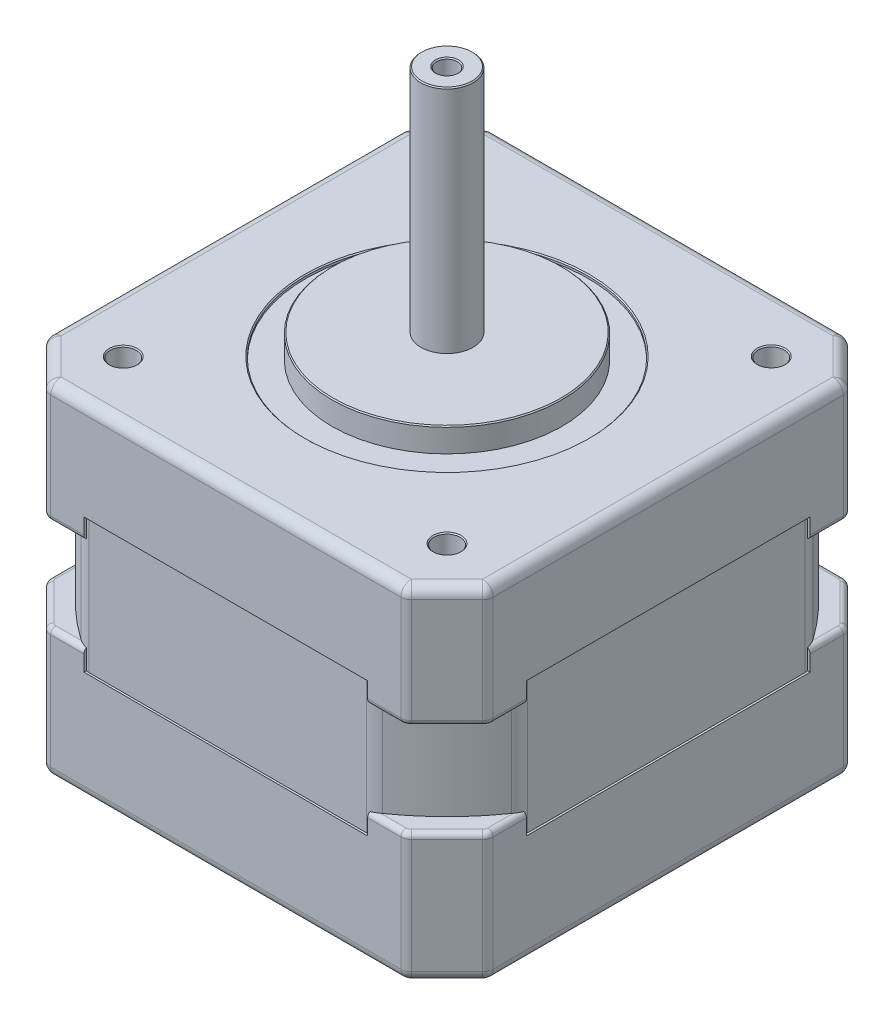
SolidWorks part; units mm, degrees
ref_plane "Front Plane" through (0, 0, 0) normal (0, 0, 1) x (1, 0, 0)
ref_plane "Top Plane" through (0, 0, 0) normal (0, 1, 0) x (1, 0, 0)
ref_plane "Right Plane" through (0, 0, 0) normal (1, 0, 0) x (0, 0, -1)
sketch "Sketch1" plane through (0, 0, 0) normal (0, 1, 0) x (1, 0, 0)
  line L0 (0, 21.15) -> (0, 0) construction
  line L1 (-21.15, 21.15) -> (-21.15, -21.15)
  line L2 (-21.15, -21.15) -> (21.15, -21.15)
  line L3 (-21.15, 21.15) -> (21.15, 21.15)
  line L4 (21.15, -21.15) -> (21.15, 21.15)
  line L5 (21.15, 0) -> (0, 0) construction
  line L6 (21.15, 21.15) -> (0, 0) construction
  circle A0 centre (15.5, 15.5) radius 1.25
  circle A1 centre (-15.4497, 15.5) radius 1.25
  circle A2 centre (-15.4497, -15.5) radius 1.25
  circle A3 centre (15.5, -15.5) radius 1.25
  dimension "D1" = 42.3
  dimension "D3" = 2.5
  dimension "D2" = 31
extrude "Boss-Extrude1" add sketch "Sketch1" against normal blind 32.8
chamfer "Chamfer1" distance 4 angle 45 4 edges at (21.15, -16.4, 21.15) (-21.15, -16.4, 21.15) (-21.15, -16.4, -21.15) (21.15, -16.4, -21.15)
sketch "Sketch2" plane through (0, 0, 0) normal (0, 1, 0) x (1, 0, 0)
  circle A0 centre (0, 0) radius 11
  dimension "D1" = 22
extrude "Boss-Extrude2" add sketch "Sketch2" along normal blind 2
sketch "Sketch6" plane through (0, -32.8, 0) normal (0, -1, 0) x (1, 0, 0)
  line L0 (-17.15, 21.15) -> (17.15, 21.15) construction
  line L1 (-21.15, -17.15) -> (-21.15, 17.15) construction
  line L2 (-17.15, 21.15) -> (-21.15, 17.15) construction
  line L3 (-17.15, 21.15) -> (-21.15, 17.15)
  line L4 (-21.15, 13.5626) -> (-21.15, 17.15)
  line L5 (-17.15, 21.15) -> (-13.5626, 21.15)
  arc A0 (-13.5626, 21.15) -> (-21.15, 13.5626) centre (0, 0) ccw
  dimension "D1" = 25.125
extrude "Cut-Extrude2" cut sketch "Sketch6" against normal offset from surface (8.85 mm away) 11.5 from offset 12.45 up to face at (0, 0, 0) offset against normal yes
pattern_circular "CirPattern1" count 4 over 360 about axis through (0, 10.7303, 0) along (0, -1, 0) of "Cut-Extrude2"
sketch "Sketch7" plane through (-21.15, 0, 0) normal (-1, 0, 0) x (0, 0, 1)
  line L0 (13.5626, -11.5) -> (13.5626, -20.35) construction
  line L1 (-13.5626, -9.5) -> (13.5626, -9.5)
  line L2 (-13.5626, -9.5) -> (-13.5626, -11.5)
  line L3 (-13.5626, -22.35) -> (13.5626, -22.35)
  line L4 (13.5626, -9.5) -> (13.5626, -11.5)
  line L5 (-13.5626, -11.5) -> (-13.5626, -20.35) construction
  line L6 (-17.15, -11.5) -> (-13.5626, -11.5) construction
  line L7 (-13.5626, -20.35) -> (-17.15, -20.35) construction
  line L8 (-21.15, -11.5) -> (-13.5626, -11.5) construction
  line L9 (-17.3563, -11.5) -> (-13.5626, -11.5)
  line L10 (-17.3563, -11.5) -> (-17.3563, -20.35)
  line L11 (-17.3563, -20.35) -> (-13.5626, -20.35)
  line L12 (19.15, -11.5) -> (19.15, -20.35)
  line L13 (21.15, -20.35) -> (17.15, -20.35) construction
  line L14 (13.5626, -11.5) -> (19.15, -11.5)
  line L15 (-13.5626, -20.35) -> (-13.5626, -22.35)
  line L16 (13.5626, -20.35) -> (13.5626, -22.35)
  line L17 (13.5626, -20.35) -> (19.15, -20.35)
  dimension "D1" = 2
  dimension "D2" = 2
extrude "Cut-Extrude3" cut sketch "Sketch7" against normal blind 0.2
pattern_circular "CirPattern2" count 4 over 360 about axis through (0, 2, 0) along (0, -1, 0) of "Cut-Extrude3"
sketch "Sketch3" plane through (0, 0, 0) normal (0, 1, 0) x (1, 0, 0)
  circle A0 centre (0, 0) radius 2.5
  dimension "D1" = 5
extrude "Boss-Extrude3" add sketch "Sketch3" along normal blind 24
sketch "Sketch8" plane through (0, -32.8, 0) normal (0, -1, 0) x (1, 0, 0)
  circle A0 centre (15.5, -15.5) radius 3.075
  circle A1 centre (15.5, 15.5) radius 3.075
  circle A2 centre (-15.4497, 15.5) radius 3.075
  circle A3 centre (-15.4497, -15.5) radius 3.075
  dimension "D1" = 6.15
extrude "Cut-Extrude4" cut sketch "Sketch8" against normal blind 2
sketch "Sketch9" plane through (0, -32.8, 0) normal (0, -1, 0) x (1, 0, 0)
  circle A0 centre (0, 0) radius 4.625
  dimension "D1" = 9.25
extrude "Cut-Extrude5" cut sketch "Sketch9" against normal blind 3
sketch "Sketch10" plane through (0, 0, -21.15) normal (0, 0, -1) x (-1, 0, 0)
  line L0 (-13.5626, -22.35) -> (13.5626, -22.35) construction
  line L1 (-4.1, -30.55) -> (4.1, -30.55)
  line L2 (-4.1, -30.55) -> (-4.1, -22.35)
  line L3 (-4.1, -22.35) -> (4.1, -22.35)
  line L4 (4.1, -30.55) -> (4.1, -22.35)
  line L5 (-4.1, -30.55) -> (4.1, -22.35) construction
  line L6 (-4.1, -22.35) -> (4.1, -30.55) construction
  line L7 (0, -11.5) -> (0, -20.35) construction
  point P0 (0, -26.45)
  dimension "D1" = 8.2
extrude "Cut-Extrude6" cut sketch "Sketch10" against normal blind 0.5
sketch "Sketch11" plane through (0, 0, 0) normal (0, 1, 0) x (1, 0, 0)
  circle A0 centre (0, 0) radius 11 construction
  circle A1 centre (0, 0) radius 11
  circle A2 centre (0, 0) radius 13.5
  dimension "D1" = 2.5
extrude "Cut-Extrude7" cut sketch "Sketch11" against normal blind 0.3
fillet "Fillet2" radius 2 8 edges at (-13.8695, -15.925, -20.95) (13.8695, -15.925, -20.95) (20.95, -15.925, -13.8695) (20.95, -15.925, 13.8695) (13.8695, -15.925, 20.95) (-13.8695, -15.925, 20.95) (-20.95, -15.925, 13.8695) (-20.95, -15.925, -13.8695)
fillet "Fillet1" radius 1 32 edges at (0, 0, 21.15) (0, -32.8, 21.15) (19.15, 0, -19.15) (19.15, -32.8, -19.15) (17.15, -5.75, -21.15) (17.15, -26.575, -21.15) (0, 0, -21.15) (0, -32.8, -21.15) (-17.15, -5.75, -21.15) (-17.15, -26.575, -21.15) (-19.15, 0, -19.15) (-19.15, -32.8, -19.15) (-21.15, -5.75, -17.15) (-21.15, -26.575, -17.15) (-21.15, 0, 0) (-21.15, -32.8, 0) (-21.15, -5.75, 17.15) (-21.15, -26.575, 17.15) (-19.15, 0, 19.15) (-17.15, -5.75, 21.15) (-17.15, -26.575, 21.15) (-19.15, -32.8, 19.15) (21.15, -5.75, -17.15) (21.15, -26.575, -17.15) (21.15, -32.8, 0) (21.15, 0, 0) (17.15, -5.75, 21.15) (17.15, -26.575, 21.15) (19.15, 0, 19.15) (21.15, -5.75, 17.15) (21.15, -26.575, 17.15) (19.15, -32.8, 19.15)
fillet "Fillet3" radius 0.5 40 edges at (21.15, -11.5, -15.1492) (21.0739, -11.5, -17.1185) (15.1492, -11.5, -21.15) (17.1185, -11.5, -21.0739) (15.1492, -20.35, -21.15) (17.1185, -20.35, -21.0739) (19.15, -20.35, -19.15) (21.0739, -20.35, -17.1185) (15.1492, -11.5, 21.15) (17.1185, -11.5, 21.0739) (21.15, -11.5, 15.1492) (21.0739, -11.5, 17.1185) (21.15, -20.35, 15.1492) (21.0739, -20.35, 17.1185) (15.1492, -20.35, 21.15) (17.1185, -20.35, 21.0739) (-21.15, -20.35, -15.1492) (-21.0739, -20.35, -17.1185) (-15.1492, -20.35, -21.15) (-17.1185, -20.35, -21.0739) (-15.1492, -20.35, 21.15) (-17.1185, -20.35, 21.0739) (-21.15, -20.35, 15.1492) (-21.0739, -20.35, 17.1185) (-21.15, -11.5, 15.1492) (-21.0739, -11.5, 17.1185) (-15.1492, -11.5, 21.15) (-17.1185, -11.5, 21.0739) (-15.1492, -11.5, -21.15) (-17.1185, -11.5, -21.0739) (-21.15, -11.5, -15.1492) (-21.0739, -11.5, -17.1185) (19.15, -11.5, -19.15) (21.15, -20.35, -15.1492) (19.15, -11.5, 19.15) (19.15, -20.35, 19.15) (-19.15, -20.35, -19.15) (-19.15, -20.35, 19.15) (-19.15, -11.5, 19.15) (-19.15, -11.5, -19.15)
chamfer "Chamfer2" distance 0.1 angle 45 6 edges at (0, 2, 11) (0, 0, 13.5) (-15.4497, 0, 16.75) (-15.4497, 0, -14.25) (15.5, 0, -14.25) (15.5, 0, 16.75)
sketch "Sketch12" plane through (0, 24, 0) normal (0, 1, 0) x (1, 0, 0)
  circle A0 centre (0, 0) radius 1
  dimension "D1" = 2
extrude "Cut-Extrude8" cut sketch "Sketch12" against normal blind 2.5
chamfer "Chamfer3" distance 0.1 angle 45 2 edges at (0, 24, 2.5) (0, 24, 1)
chamfer "Chamfer4" distance 0.3 angle 45 5 edges at (15.5, -32.8, -18.575) (15.5, -32.8, 12.425) (-15.4497, -32.8, 12.425) (-15.4497, -32.8, -18.575) (0, -32.8, -4.625)
sketch "Sketch13" plane through (0, 0, -20.65) normal (0, 0, -1) x (-1, 0, 0)
  line L0 (-2.025, -29.05) -> (2.025, -29.05) construction
  line L4 (-4.1, -30.55) -> (4.1, -30.55) construction
  line L8 (0, -29.8) -> (0, -32.5) construction
  circle A0 centre (-2.025, -29.05) radius 0.65
  circle A1 centre (-0.675, -29.05) radius 0.65
  circle A2 centre (0.675, -29.05) radius 0.65
  circle A3 centre (2.025, -29.05) radius 0.65
  point P8 (0, -29.05)
  dimension "D1" = 1.3
  dimension "D3" = 1.35
  dimension "D2" = 1.5
  dimension "D4" = 1.35
  dimension "D5" = 1.35
extrude "Boss-Extrude5" add sketch "Sketch13" along normal blind 5.5
sketch "Sketch5" plane through (-12.85, -32.8, 0) normal (0, 1, 0) x (0, 0, -1)
  line L0 (-20.15, -7.0234) -> (20.15, -7.0234) construction
  line L1 (20.15, 3.8858) -> (20.15, -29.5858) construction
  line L2 (-20.15, -29.5858) -> (-20.15, 3.8858) construction
  text T0 "http://multilogica-shop.com\r\nMOTOR\r\nPASSO A PASSO\r\nCód:MOT0030033\r\n" font "Century Gothic" height 1.5
extrude "Cut-Extrude1" cut sketch "Sketch5" along normal blind 0.3
equation "\"D2@Sketch7\"=\"D1@Sketch7\""
